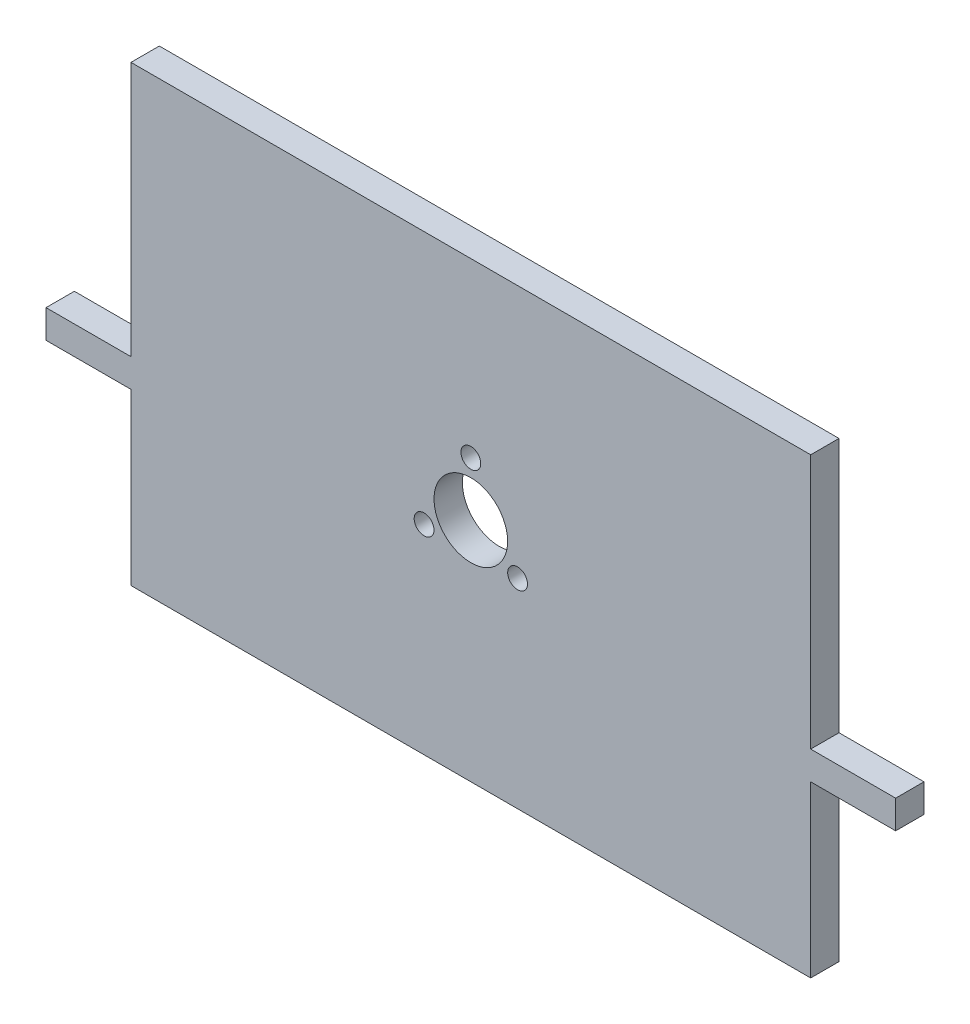
SolidWorks part; units mm, degrees
ref_plane "前视基准面" through (0, 0, 0) normal (0, 0, 1) x (1, 0, 0)
ref_plane "上视基准面" through (0, 0, 0) normal (0, 1, 0) x (1, 0, 0)
ref_plane "右视基准面" through (0, 0, 0) normal (1, 0, 0) x (0, 0, -1)
other "Configuration Table"
sketch "草图1" plane through (0, 0, 0) normal (0, 0, 1) x (1, 0, 0)
  line L1 (60, -45) -> (-60, -45)
  line L2 (60, -45) -> (60, 45)
  line L3 (60, 45) -> (-60, 45)
  line L4 (-60, -45) -> (-60, 45)
  line L5 (60, -45) -> (-60, 45) construction
  line L6 (60, 45) -> (-60, -45) construction
  point P0 (0, 0)
  dimension "D1" = 120
  dimension "D2" = 90
extrude "凸台-拉伸1" add sketch "草图1" along normal blind 5
sketch "草图5" plane through (0, 0, 0) normal (0, 0, -1) x (-1, 0, 0)
  line L0 (60, 45) -> (60, -45) construction
  line L1 (-60, -45) -> (60, -45)
  line L2 (-60, -45) -> (-60, -35)
  line L3 (-60, -35) -> (60, -35)
  line L4 (60, -45) -> (60, -35)
  dimension "D1" = 10
extrude "切除-拉伸3" cut sketch "草图5" against normal blind 10
sketch "草图8" plane through (60, 0, 0) normal (1, 0, 0) x (0, 0, -1)
  line L0 (0, 0.0974) -> (0, -5.0026)
  line L1 (0, -35) -> (0, 45) construction
  line L2 (-50.9779, 0.0974) -> (47.0221, 0.0974) construction
  line L3 (47.0221, -5.0026) -> (-50.9779, -5.0026) construction
  line L4 (0, -5.0026) -> (-5, -5.0026)
  line L5 (-5, -35) -> (-5, 45) construction
  line L6 (-5, -5.0026) -> (-5, 0.0974)
  line L7 (-5, 0.0974) -> (0, 0.0974)
  line L9 (-4.95, -5.0026) -> (-0.05, -5.0026)
  line L10 (-4.95, -5.0026) -> (-4.95, 0.0974)
  line L11 (-4.95, 0.0974) -> (-0.05, 0.0974)
  line L12 (-0.05, -5.0026) -> (-0.05, 0.0974)
  line L13 (-4.95, -5.0026) -> (-0.05, 0.0974) construction
  line L14 (-4.95, 0.0974) -> (-0.05, -5.0026) construction
  point P8 (-2.5, -2.4526)
  dimension "D1" = 0.05
  dimension "D2" = 0.05
  dimension "D3" = 0
  dimension "D4" = 0
sketch "草图10" plane through (60, 0, 0) normal (1, 0, 0) x (0, 0, -1)
  line L0 (-5, -35) -> (-5, 45) construction
  line L1 (0, 0) -> (-5, 0)
  line L2 (-5, 0) -> (-5, -5.0026)
  line L3 (-5, -5.0026) -> (0, -5.0026)
  line L4 (0, -35) -> (0, 45) construction
  line L5 (0, -5.0026) -> (0, 0)
extrude "凸台-拉伸3" add sketch "草图10" along normal blind 15
sketch "草图11" plane through (0, 0, 0) normal (0, 0, -1) x (-1, 0, 0)
  line L0 (0, 45) -> (0, -35) construction
  line L1 (-60, 45) -> (60, 45) construction
  line L2 (60, -35) -> (-60, -35) construction
sketch "草图12" plane through (-60, 0, 0) normal (-1, 0, 0) x (0, 0, 1)
  line L4 (0, 45) -> (0, -35)
  line L5 (0, -35) -> (5, -35)
  line L6 (5, -35) -> (5, 45)
  line L7 (5, 45) -> (0, 45)
  line L8 (0, 45) -> (0, -35)
  line L9 (0, -35) -> (5, -35)
  line L10 (5, -35) -> (5, 45)
  line L11 (5, 45) -> (0, 45)
  line L12 (0, 0) -> (0, -5.0026)
  line L13 (5, 0) -> (0, 0)
  line L14 (5, -5.0026) -> (5, 0)
  line L15 (0, -5.0026) -> (5, -5.0026)
  line L16 (0, 0) -> (0, -5.0026)
  line L17 (5, 0) -> (0, 0)
  line L18 (5, -5.0026) -> (5, 0)
  line L19 (0, -5.0026) -> (5, -5.0026)
  dimension "D1" = 0
  dimension "D2" = 0
extrude "凸台-拉伸4" add sketch "草图12" along normal blind 15 contours L8 L19 L10 L17 region at (-60, -2.5013, 2.5)
sketch "草图13" plane through (0, 0, 5) normal (0, 0, 1) x (1, 0, 0)
  line L0 (-60, 45) -> (60, -35) construction
  line L1 (60, 45) -> (-60, -35) construction
  circle A0 centre (0, 5) radius 6.5
  circle A1 centre (8.2532, 0.235) radius 1.75
  circle A2 centre (-8.2532, 0.235) radius 1.75
  circle A3 centre (0, 5) radius 9.53
  circle A4 centre (0, 14.53) radius 1.75
  point P19 (0, 5)
  dimension "D1" = 13
  dimension "D2" = 19.06
  dimension "D3" = 3.5
  dimension "D4" = 3
extrude "切除-拉伸4" cut sketch "草图13" against normal blind 15 contours A0 | A3 A4 | A3 A4 | A3 A2 | A2 A3 | A3 A1 | A1 A3 region at (0, 5, 5) region at (8.8707, -0.1215, 5) region at (7.5856, 0.6205, 5) region at (-7.5856, 0.6205, 5) region at (-8.8707, -0.1215, 5) region at (0, 13.7591, 5) region at (0, 15.243, 5)
